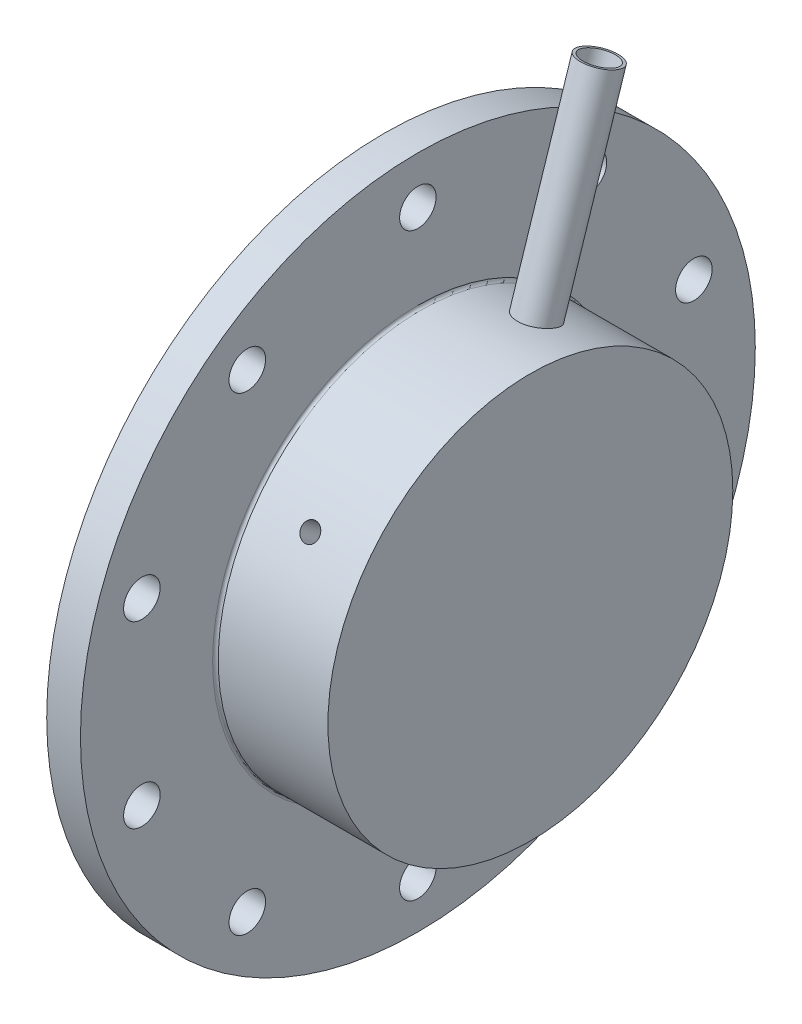
SolidWorks part; units mm, degrees
material "AISI 316 Stainless Steel Sheet (SS)"
ref_plane "Front Plane" through (0, 0, 0) normal (0, 0, 1) x (1, 0, 0)
ref_plane "Top Plane" through (0, 0, 0) normal (0, 1, 0) x (1, 0, 0)
ref_plane "Right Plane" through (0, 0, 0) normal (1, 0, 0) x (0, 0, -1)
sketch "Sketch1" plane through (0, 0, 0) normal (1, 0, 0) x (0, 0, -1)
  line L0 (0, 0) -> (0, 60) construction
  line L1 (0, 0) -> (0, 51.6) construction
  circle A0 centre (0, 0) radius 31
  circle A1 centre (0, 0) radius 60
  circle A2 centre (0, 51.6) radius 3.25
  circle A3 centre (30.3297, 41.7453) radius 3.25
  circle A4 centre (49.0745, 15.9453) radius 3.25
  circle A5 centre (49.0745, -15.9453) radius 3.25
  circle A6 centre (30.3297, -41.7453) radius 3.25
  circle A7 centre (0, -51.6) radius 3.25
  circle A8 centre (-30.3297, -41.7453) radius 3.25
  circle A9 centre (-49.0745, -15.9453) radius 3.25
  circle A10 centre (-49.0745, 15.9453) radius 3.25
  circle A11 centre (-30.3297, 41.7453) radius 3.25
  point P23 (0, 0)
  point P24 (0, 0)
  dimension "D1" = 62
  dimension "D2" = 120
  dimension "D5" = 6.5
  dimension "D4" = 51.6
  dimension "D6" = 10
extrude "Boss-Extrude1" add sketch "Sketch1" along normal blind 6
ref_plane "Plane1" through (2.5, 0, 0) normal (0, -1, 0) x (0, 0, -1)
ref_plane "Plane2" through (2.5, 0, 0) normal (0, -1, 0) x (0, 0, -1)
ref_plane "Plane3" through (-20, 0, 0) normal (0, -1, 0) x (0, 0, 1)
ref_plane "Plane4" through (-20, 0, 0) normal (0, -1, 0) x (0, 0, 1)
ref_plane "Plane5" through (-20, 0, 0) normal (0, -1, 0) x (0, 0, 1)
ref_plane "Plane6" through (0, 0, 0) normal (0, -1, 0) x (0, 0, 1)
sketch "Sketch7" plane through (0, 0, 0) normal (0, -1, 0) x (0, 0, 1)
  line L0 (35, -1.2436) -> (34.8912, 0)
  line L1 (34.8912, 0) -> (38.1088, 0)
  line L2 (38.1088, 0) -> (38, -1.2436)
  line L3 (37.5019, -1.7) -> (35.4981, -1.7)
  line L4 (0, 50) -> (0, -50) construction
  arc A0 (38, -1.2436) -> (37.5019, -1.7) centre (37.5019, -1.2) cw
  arc A1 (35.4981, -1.7) -> (35, -1.2436) centre (35.4981, -1.2) cw
ref_plane "Plane7" through (6, 0, 0) normal (1, 0, 0) x (0, 0, -1)
sketch "Sketch8" plane through (6, 0, 0) normal (1, 0, 0) x (0, 0, -1)
  circle A0 centre (0, 0) radius 36
  circle A2 centre (0, 0) radius 3
  dimension "D1" = 72
  dimension "D2" = 6
extrude "Boss-Extrude2" add sketch "Sketch8" along normal blind 20
ref_plane "Plane8" through (26, 0, 0) normal (1, 0, 0) x (0, 0, -1)
ref_plane "Plane9" through (16, 0, 0) normal (1, 0, 0) x (0, 0, -1)
ref_plane "Plane10" through (0, 20, 0) normal (0, 1, 0) x (1, 0, 0)
sketch "Sketch15" plane through (26, 0, 0) normal (1, 0, 0) x (0, 0, -1)
  point P0 (0, 0)
sketch "Sketch16" plane through (16, 0, 0) normal (1, 0, 0) x (0, 0, -1)
  line L0 (0, 0) -> (-44.9907, 32.6877) construction
  line L1 (0, 0) -> (44.3352, 32.2114) construction
  line L2 (0, 0) -> (0, 37.7696) construction
  line L3 (44.3352, 32.2114) -> (43.3948, 33.5059)
  line L4 (43.3948, 33.5059) -> (0, 1.9777)
  line L5 (0, 1.9777) -> (0, 0)
  line L6 (44.3352, 32.2114) -> (0, 0)
  line L7 (0, 1.9777) -> (-37.0814, 28.9189) construction
  line L8 (-37.0814, 28.9189) -> (-38.0218, 27.6245) construction
  line L9 (-38.0218, 27.6245) -> (0, 0) construction
  dimension "D1" = 54
  dimension "D2" = 108
  dimension "D3" = 1.6
  dimension "D4" = 1.6
revolve "Cut-Revolve4" cut sketch "Sketch16" angle 360 about L1
sketch "Sketch28" plane through (16, 0, -13) normal (-1, 0, 0) x (0, 0, 1)
  line L0 (4.4914, 6.1819) -> (-40.4993, 38.8695) construction
  line L1 (4.4914, -6.1819) -> (48.8266, 26.0296) construction
  line L2 (13, 0) -> (13, 37.7696) construction
  line L3 (48.8266, 26.0296) -> (47.8862, 27.324)
  line L4 (47.8862, 27.324) -> (13, 1.9777)
  line L5 (13, 1.9777) -> (13, 0)
  line L6 (48.8266, 26.0296) -> (13, 0)
  line L7 (13, 1.9777) -> (-32.59, 35.1008) construction
  line L8 (-32.59, 35.1008) -> (-33.5304, 33.8063) construction
  line L9 (-33.5304, 33.8063) -> (13, 0) construction
  dimension "D1" = 54
  dimension "D2" = 108
  dimension "D3" = 1.6
  dimension "D4" = 1.6
revolve "Cut-Revolve5" cut sketch "Sketch28" angle 360 about L1
fillet "Fillet1" radius 0.5 1 edges at (6, 0, -36)
ref_axis "Axis1" through (26, 0, 0) along (-1, 0, 0)
ref_plane "Plane12" through (0, 0, 0) normal (0, 0.9511, -0.309) x (-1, 0, 0)
sketch "Sketch29" plane through (0, 0, 0) normal (0, 0.9511, -0.309) x (1, 0, 0)
  line L0 (26, -36) -> (26, 36) construction
  circle A0 centre (16, 0) radius 3
  dimension "D1" = 6
  dimension "D2" = 10
extrude "Cut-Extrude1" cut sketch "Sketch29" along normal blind 51
ref_plane "Plane13" through (0, 34.238, -11.1246) normal (0, 0.9511, -0.309) x (-1, 0, 0)
sketch "Sketch32" plane through (0, 34.238, -11.1246) normal (0, 0.9511, -0.309) x (-1, 0, 0)
  circle A0 centre (-16, 0) radius 3
  circle A1 centre (-16, 0) radius 3.5
  dimension "D1" = 6
  dimension "D2" = 7
extrude "Boss-Extrude4" add sketch "Sketch32" along normal blind 36 and the other way up to surface other way up to face at (16.3662, 19.8804, 30.0128)
sketch "Sketch33" plane through (0, 0, 0) normal (0, 0, 1) x (1, 0, 0)
  line L0 (0, 60) -> (0, -60) construction
  line L1 (0, 46.545) -> (2.17, 46.545)
  line L2 (0, 44.9953) -> (0, 38.4953) construction
  line L3 (0, 40.195) -> (2.17, 40.195)
  line L4 (2.67, 39.695) -> (2.67, 36.095)
  line L5 (2.17, 35.595) -> (0, 35.595)
  line L6 (0, 35.595) -> (0, 40.195)
  line L7 (2.67, 46.045) -> (2.67, 42.445)
  line L8 (2.17, 41.945) -> (0, 41.945)
  line L9 (0, 41.945) -> (0, 46.545)
  arc A0 (2.67, 39.695) -> (2.17, 40.195) centre (2.17, 39.695) ccw
  arc A1 (2.17, 35.595) -> (2.67, 36.095) centre (2.17, 36.095) ccw
  arc A2 (2.67, 46.045) -> (2.17, 46.545) centre (2.17, 46.045) ccw
  arc A3 (2.17, 41.945) -> (2.67, 42.445) centre (2.17, 42.445) ccw
  point P0 (0, 37.895)
  point P1 (0, 44.245)
  point P17 (2.67, 40.195)
  point P20 (2.67, 35.595)
  dimension "D7" = 0.5
  dimension "D8" = 0.5
  dimension "D9" = 0.5
  dimension "D10" = 0.5
  dimension "D1" = 37.895
  dimension "D2" = 44.245
  dimension "D3" = 2.3
  dimension "D4" = 4.6
  dimension "D5" = 2.67
  dimension "D6" = 2.3
revolve "Cut-Revolve6" cut sketch "Sketch33" angle 360 about axis through (26, 0, 0) along (-1, 0, 0)
sketch "Sketch34" plane through (26, 0, 0) normal (1, 0, 0) x (0, 0, -1)
  circle A0 centre (0, 0) radius 3
extrude "Boss-Extrude5" add sketch "Sketch34" against normal blind 7
equation "\"D4@Sketch1\"=60-8.4"
equation "\"D1@Sketch33\"=75.79/2"
equation "\"D2@Sketch33\"=88.49/2"
equation "\"D6@Sketch33\"=\"D3@Sketch33\""
